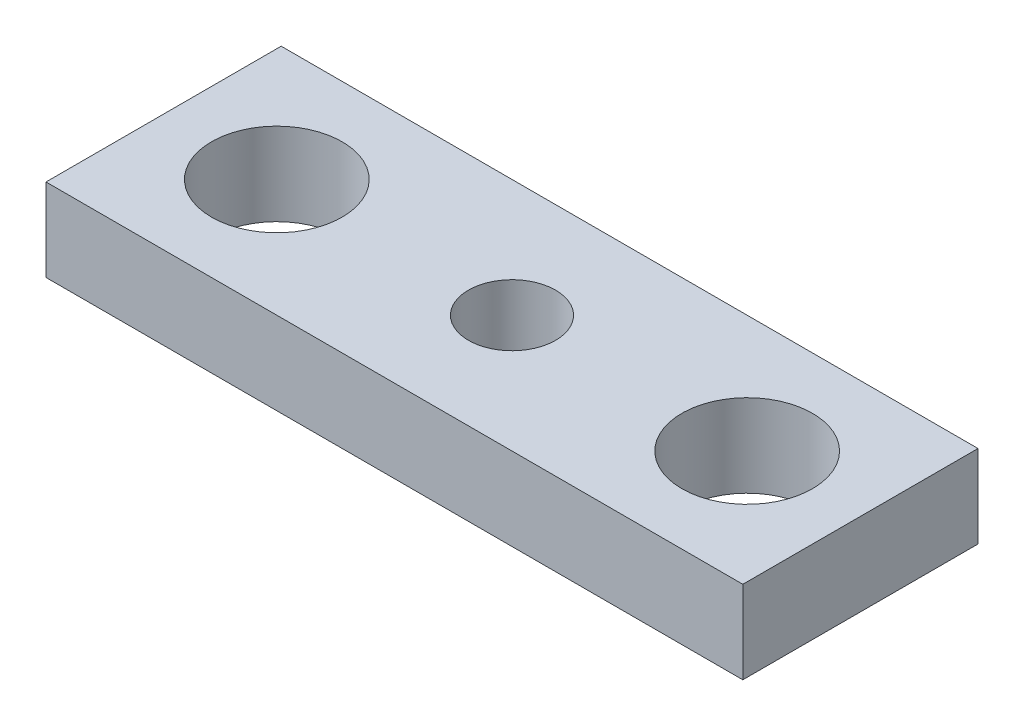
SolidWorks part; units mm, degrees
ref_plane "前视基准面" through (0, 0, 0) normal (0, 0, 1) x (1, 0, 0)
ref_plane "上视基准面" through (0, 0, 0) normal (0, 1, 0) x (1, 0, 0)
ref_plane "右视基准面" through (0, 0, 0) normal (1, 0, 0) x (0, 0, -1)
sketch "草图1" plane through (0, 0, 0) normal (0, 1, 0) x (1, 0, 0)
  line L1 (-40, 13.5) -> (40, 13.5)
  line L2 (-40, 13.5) -> (-40, -13.5)
  line L3 (-40, -13.5) -> (40, -13.5)
  line L4 (40, 13.5) -> (40, -13.5)
  line L5 (-40, 13.5) -> (40, -13.5) construction
  line L6 (-40, -13.5) -> (40, 13.5) construction
  point P0 (0, 0)
  dimension "D1" = 80
  dimension "D2" = 27
extrude "凸台-拉伸1" add sketch "草图1" along normal blind 9.5
sketch "草图2" plane through (0, 0, 0) normal (0, -1, 0) x (1, 0, 0)
  line L0 (-40, 0) -> (40, 0) construction
  line L1 (-40, -13.5) -> (-40, 13.5) construction
  line L2 (40, 13.5) -> (40, -13.5) construction
ref_plane "基准面1" through (0, 0, 0) normal (0, 0, 1) x (1, 0, 0)
sketch "草图3" plane through (0, 9.5, 0) normal (0, 1, 0) x (1, 0, 0)
  line L0 (-14.85, 0) -> (14.85, 0) construction
  line L1 (0, 13.5) -> (0, -13.5) construction
  line L2 (40, 13.5) -> (-40, 13.5) construction
  line L3 (-40, -13.5) -> (40, -13.5) construction
  circle A0 centre (-27, 0) radius 7.5
  circle A1 centre (27, 0) radius 7.5
  dimension "D1" = 15
  dimension "D2" = 54
extrude "切除-拉伸1" cut sketch "草图3" against normal through all contours A1 | A0
sketch "草图7" plane through (-40, 0, 0) normal (-1, 0, 0) x (0, 0, 1)
  line L0 (-13.5, 4.75) -> (13.5, 4.75) construction
  line L1 (-13.5, 9.5) -> (-13.5, 0) construction
  line L2 (13.5, 9.5) -> (13.5, 0) construction
ref_plane "基准面3" through (0, 4.75, 0) normal (0, 1, 0) x (1, 0, 0)
sketch "草图9" plane through (0, 4.75, 0) normal (0, 1, 0) x (1, 0, 0)
  line L0 (-44.1863, 9.5) -> (43.8901, 9.5) construction
  line L1 (40, 13.5) -> (-40, 13.5) construction
  line L2 (-40, -9.5) -> (39.6508, -9.5) construction
  line L3 (-40, 13.5) -> (-40, -13.5) construction
  line L4 (-40, -13.5) -> (40, -13.5) construction
  dimension "D1" = 4
  dimension "D2" = 4
sketch "草图10" plane through (0, 0, 0) normal (0, -1, 0) x (1, 0, 0)
  circle A0 centre (0, 0) radius 5
  dimension "D1" = 10
extrude "切除-拉伸2" cut sketch "草图10" against normal through all
